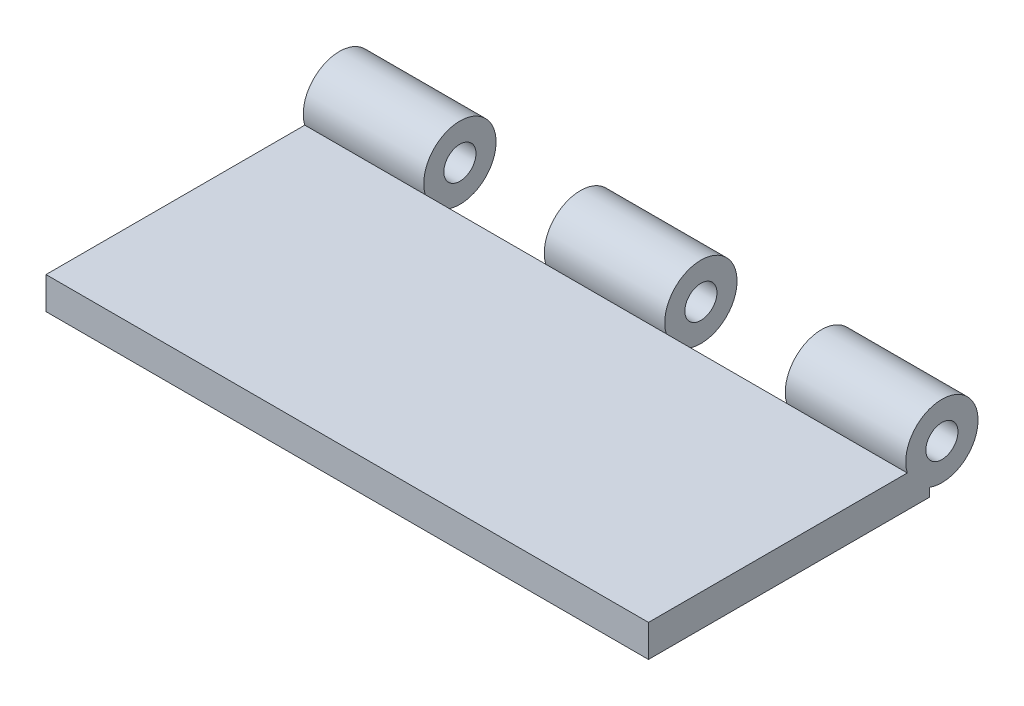
SolidWorks part; units mm, degrees
ref_plane "Front Plane" through (0, 0, 0) normal (0, 0, 1) x (1, 0, 0)
ref_plane "Top Plane" through (0, 0, 0) normal (0, 1, 0) x (1, 0, 0)
ref_plane "Right Plane" through (0, 0, 0) normal (1, 0, 0) x (0, 0, -1)
sketch "Sketch1" plane through (0, 0, 0) normal (0, 1, 0) x (1, 0, 0)
  line L1 (-101.1962, 19.5813) -> (48.8038, 19.5813)
  line L2 (-101.1962, 19.5813) -> (-101.1962, -50.4187)
  line L3 (-101.1962, -50.4187) -> (48.8038, -50.4187)
  line L4 (48.8038, 19.5813) -> (48.8038, -50.4187)
  line L5 (-101.1962, 19.5813) -> (48.8038, -50.4187) construction
  line L6 (-101.1962, -50.4187) -> (48.8038, 19.5813) construction
  point P0 (-26.1962, -15.4187)
  dimension "D1" = 150
  dimension "D2" = 70
extrude "Boss-Extrude1" add sketch "Sketch1" along normal blind 8
ref_plane "Plane1" through (-101.1962, 0, 0) normal (-1, 0, 0) x (0, 0, 1)
sketch "Sketch2" plane through (-101.1962, 0, 0) normal (-1, 0, 0) x (0, 0, 1)
  line L0 (-19.5813, 8) -> (-22.631, 10.5883)
  circle A0 centre (-22.631, 10.5883) radius 4
  circle A1 centre (-22.631, 10.5883) radius 9
extrude "Boss-Extrude2" add sketch "Sketch2" against normal blind 30 contours A1 A0 region at (-101.1962, 10.5883, -31.3765)
ref_plane "Plane2" through (0, 4, 0) normal (0, -1, 0) x (-1, 0, 0)
pattern_linear "LPattern1" count 3 spacing 60 along (1, 0, 0) of "Boss-Extrude2"
sketch "Sketch4" plane through (-101.1962, 0, 0) normal (-1, 0, 0) x (0, 0, 1)
  circle A0 centre (-22.631, 10.5883) radius 9
extrude "Cut-Extrude1" cut sketch "Sketch4" against normal blind 30 from offset 90 offset against normal yes
sketch "Sketch5" plane through (-101.1962, 0, 0) normal (-1, 0, 0) x (0, 0, 1)
  circle A0 centre (-22.631, 10.5883) radius 9
extrude "Cut-Extrude2" cut sketch "Sketch5" against normal blind 30 from offset 30 offset against normal yes
scale "Scale1" scale about centroid uniform scaling yes scale factor 0.333333
